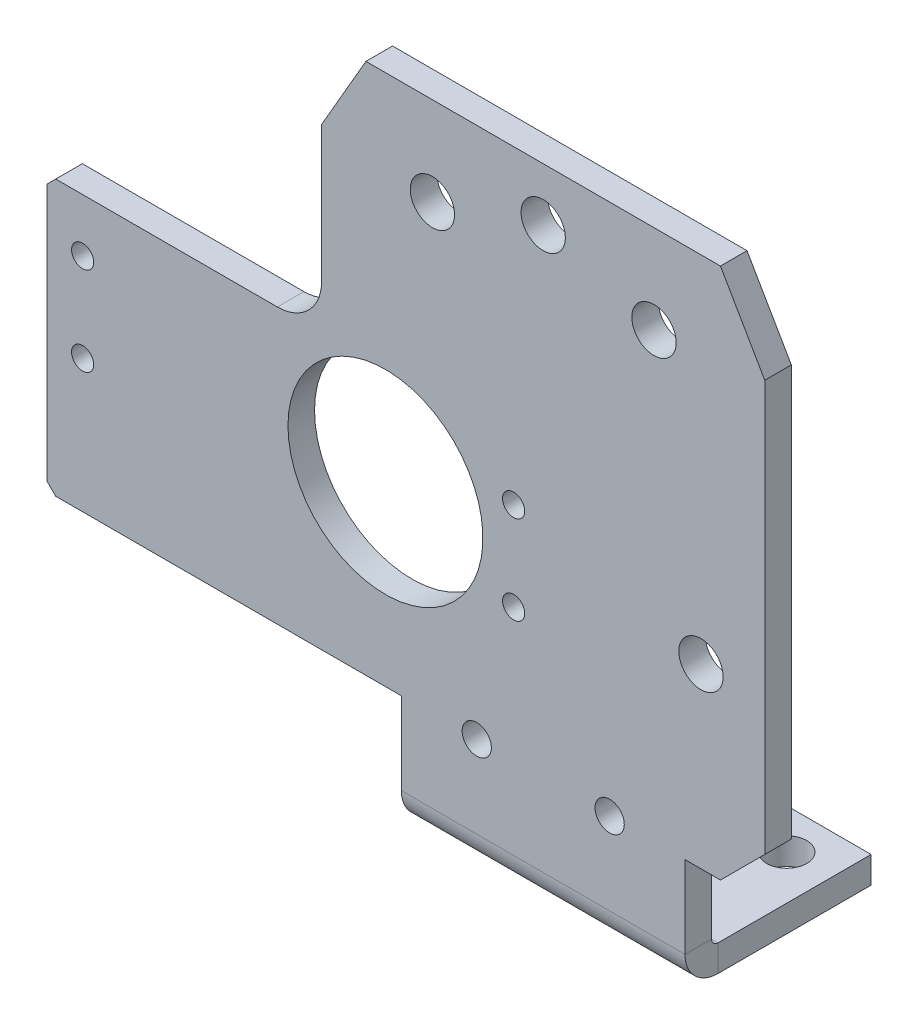
SolidWorks part; units mm, degrees
note: The reader was unsure of these and kept them because the rebuilt part matched: flange length of "边线-法兰1".
material "Q235"
ref_plane "前视基准面" through (0, 0, 0) normal (0, 0, 1) x (1, 0, 0)
ref_plane "上视基准面" through (0, 0, 0) normal (0, 1, 0) x (1, 0, 0)
ref_plane "右视基准面" through (0, 0, 0) normal (1, 0, 0) x (0, 0, -1)
sketch "草图1" plane through (0, 0, 0) normal (0, 0, 1) x (1, 0, 0)
  line L0 (-20, -25) -> (-20, 35) construction
  line L1 (20, -25) -> (16, -25)
  line L2 (16, -25) -> (16, -35)
  line L3 (-16, -25) -> (-56, -25)
  line L4 (-20, -25) -> (-20, -35) construction
  line L5 (-20, 35) -> (20, 35)
  line L6 (20, 35) -> (20, -25) construction
  line L7 (16, -35) -> (-16, -35)
  line L8 (-20, 35) -> (-25, 26.3397)
  line L9 (-56, -25) -> (-56, 6)
  line L10 (-56, 6) -> (-25, 6)
  line L11 (-16, -25) -> (-16, -35)
  line L12 (-20, -35) -> (-16, -35) construction
  line L13 (16, -35) -> (20, -35) construction
  line L14 (20, -25) -> (20, -35) construction
  line L15 (0, -35) -> (0, 35) construction
  line L16 (20, -25) -> (25, -20)
  line L17 (25, 26.3397) -> (20, 35)
  line L18 (25, -20) -> (25, 26.3397)
  line L19 (-25, 26.3397) -> (-25, 6)
  dimension "D1" = 40
  dimension "D2" = 5
  dimension "D3" = 60
  dimension "D4" = 31
  dimension "D5" = 30
  dimension "D6" = 70
  dimension "D7" = 32
  dimension "D8" = 81
  dimension "D9" = 25
  dimension "D10" = 60
  dimension "D11" = 45
  dimension "D12" = 25
base flange "基体-法兰1" sketch "草图1" thickness 3 reverse thickness direction no parameters "D1"=0.7366
sketch "草图6" plane through (0, 0, 0) normal (0, 0, 1) x (1, 0, 0)
  line L0 (0, 0) -> (0, 29) construction
  line L1 (-17.8, -5) -> (17.8, -5) construction
  line L2 (20, 35) -> (-20, 35) construction
  circle A0 centre (-17.8, -5) radius 2.5
  circle A1 centre (17.8, -5) radius 2.5
  circle A2 centre (0, 29) radius 2.5
  circle A3 centre (-12.5, 25) radius 2.5
  circle A4 centre (12.5, 25) radius 2.5
  dimension "D1" = 35.6
  dimension "D3" = 5
  dimension "D5" = 5
  dimension "D6" = 25
  dimension "D7" = 10
  dimension "D8" = 5
  dimension "D2" = 40
  dimension "D4" = 6
extrude "切除-拉伸1" cut sketch "草图6" against normal blind 3 normal cut yes
sketch "草图9" plane through (0, 0, -3) normal (0, 0, -1) x (-1, 0, 0)
  circle A1 centre (17.8, -5) radius 11
  dimension "D1" = 22
extrude "切除-拉伸2" cut sketch "草图9" against normal up to next normal cut yes
hole_wizard "M3 螺纹孔1" positions "草图12" profile "草图13" tap size "M3" standard "Gb"
sketch "草图12" plane through (0, -38, 0) normal (0, 0, 1) x (-1, 0, 0)
  point P0 (51.965, -38)
  point P3 (51.965, -28)
  point P6 (3.335, -28)
  point P9 (3.335, -38)
sketch "草图13" plane through (-51.965, 0, 0) normal (1, 0, 0) x (0, -1, 0)
  line L0 (0, 0) -> (0, 8.2511)
  line L1 (0, 8.2511) -> (1.25, 7.5)
  line L2 (1.25, 7.5) -> (1.25, 0)
  line L3 (1.25, 0) -> (0, 0)
  line L4 (0, 8.2511) -> (-1.25, 7.5) construction
  line L5 (0, -6.35) -> (0, 107.95) construction
  dimension "螺纹孔钻头直径" = 2.5
  dimension "螺纹孔钻头深度" = 7.5
  dimension "导头角度" = 118
cosmetic thread "孔螺蚊线1"
cosmetic thread "孔螺蚊线2"
cosmetic thread "孔螺蚊线3"
cosmetic thread "孔螺蚊线4"
edge flange "边线-法兰1" sketch "草图18" flange angle 90 flange length 18 flange position material outside bend radius 0.7366 thickness 3 relief rectangular parameters "D6"=10
sketch "草图18" plane through (0, -35, -3) normal (0, 1, 0) x (1, 0, 0)
  line L1 (16, 0) -> (-16, 0) construction
  line L2 (-16, 0) -> (-16, 18)
  line L3 (-16, 18) -> (16, 18)
  line L4 (16, 18) -> (16, 0)
  line L5 (16, 0) -> (-16, 0)
bend "边线折弯1" bend radius 0.7366 bend angle 90 parameters "D5"=1
hole_wizard "Ø7.0 (7) 直径孔" positions "草图21" profile "草图22" hole size "Ø7.0" standard "Gb"
sketch "草图21" plane through (-9.85, -35, 1.271) normal (0, 1, 0) x (1, 0, 0)
  point P0 (9.85, 9.75)
sketch "草图22" plane through (0, -35, -8.479) normal (1, 0, 0) x (0, 0, 1)
  line L0 (0, 0) -> (0, 8.103)
  line L1 (0, 8.103) -> (3.5, 6)
  line L2 (3.5, 6) -> (3.5, 0)
  line L3 (3.5, 0) -> (0, 0)
  line L4 (0, 8.103) -> (-3.5, 6) construction
  line L5 (0, -6.35) -> (0, 107.95) construction
  dimension "孔直径" = 7
  dimension "孔深度" = 6
  dimension "导头角度" = 118
fillet "圆角1" radius 5 1 edges at (-25, 6, -1.5)
chamfer "倒角1" distance 1 angle 45 2 edges at (-56, -25, -1.5) (-56, 6, -1.5)
hole_wizard "Ø4.5 (4.5) 直径孔1" positions "草图23" profile "草图24" hole size "Ø4.5" standard "Gb"
sketch "草图23" plane through (-9.85, -35, 1.271) normal (0, 1, 0) x (1, 0, 0)
  point P0 (-1.15, 17.75)
  point P3 (20.85, 17.75)
sketch "草图24" plane through (-11, -35, -16.479) normal (1, 0, 0) x (0, 0, 1)
  line L0 (0, 0) -> (0, 6.3519)
  line L1 (0, 6.3519) -> (2.25, 5)
  line L2 (2.25, 5) -> (2.25, 0)
  line L3 (2.25, 0) -> (0, 0)
  line L4 (0, 6.3519) -> (-2.25, 5) construction
  line L5 (0, -6.35) -> (0, 107.95) construction
  dimension "孔直径" = 4.5
  dimension "孔深度" = 5
  dimension "导头角度" = 118
hole_wizard "M4 螺纹孔1" positions "草图27" profile "草图28" tap size "M4" standard "Gb"
sketch "草图27" plane through (-9.85, -49.5, 0) normal (0, 0, 1) x (-1, 0, 0)
  point P0 (-2.35, -24.5)
  point P3 (-17.35, -24.5)
sketch "草图28" plane through (-7.5, -25, 0) normal (1, 0, 0) x (0, -1, 0)
  line L0 (0, 0) -> (0, 12.4914)
  line L1 (0, 12.4914) -> (1.65, 11.5)
  line L2 (1.65, 11.5) -> (1.65, 0)
  line L3 (1.65, 0) -> (0, 0)
  line L4 (0, 12.4914) -> (-1.65, 11.5) construction
  line L5 (0, -6.35) -> (0, 107.95) construction
  dimension "螺纹孔钻头直径" = 3.3
  dimension "螺纹孔钻头深度" = 11.5
  dimension "导头角度" = 118
cosmetic thread "孔螺蚊线5"
cosmetic thread "孔螺蚊线6"
sketch "折弯-线1" plane through (0, 0, 0) normal (0, 1, 0) x (1, 0, 0)
sketch "边界框1" plane through (0, 0, 0) normal (0, 1, 0) x (1, 0, 0)
sheet metal parameters "钣金(11)" thickness 3 parameters "D1"=0.7366
flat pattern "平板型式(11)" [suppressed]
sketch "折弯-线2" plane through (0, 0, 0) normal (0, 1, 0) x (1, 0, 0)
sketch "边界框2" [suppressed] plane through (0, 0, 0) normal (0, 1, 0) x (1, 0, 0)
sheet metal parameters "钣金(12)" thickness 3 parameters "D1"=0.7366
flat pattern "平板型式(11)"
sketch "折弯-线3" plane through (0, 0, 0) normal (0, 1, 0) x (1, 0, 0)
sketch "边界框3" [suppressed] plane through (0, 0, 0) normal (0, 1, 0) x (1, 0, 0)
sheet metal parameters "钣金(13)" thickness 3 parameters "D1"=0.7366
flat pattern "平板型式(11)"
sketch "折弯-线4" plane through (0, 0, 0) normal (0, 1, 0) x (1, 0, 0)
sketch "边界框4" [suppressed] plane through (0, 0, 0) normal (0, 1, 0) x (1, 0, 0)
sheet metal parameters "钣金(14)" thickness 3 parameters "D1"=0.7366
flat pattern "平板型式(11)"
sketch "折弯-线5" plane through (0, 0, 0) normal (0, 1, 0) x (1, 0, 0)
sketch "边界框5" [suppressed] plane through (0, 0, 0) normal (0, 1, 0) x (1, 0, 0)
sheet metal parameters "钣金(15)" thickness 3 parameters "D1"=0.7366
flat pattern "平板型式(11)" [suppressed]
sketch "折弯-线6" plane through (0, 0, 0) normal (0, 1, 0) x (1, 0, 0)
sketch "边界框6" [suppressed] plane through (0, 0, 0) normal (0, 1, 0) x (1, 0, 0)
bend of the flat pattern "展开-<边线折弯1>1"
sheet metal parameters "钣金(16)" thickness 3 parameters "D1"=0.7366
flat pattern "平板型式(11)" [suppressed]
sketch "折弯-线7" plane through (0, 0, 0) normal (0, 1, 0) x (1, 0, 0)
sketch "边界框7" [suppressed] plane through (0, 0, 0) normal (0, 1, 0) x (1, 0, 0)
bend of the flat pattern "展开-<边线折弯1>2"
sheet metal parameters "钣金(17)" thickness 3 parameters "D1"=0.7366
flat pattern "平板型式(11)" [suppressed]
sketch "折弯-线8" plane through (0, 0, 0) normal (0, 1, 0) x (1, 0, 0)
sketch "边界框8" [suppressed] plane through (0, 0, 0) normal (0, 1, 0) x (1, 0, 0)
bend of the flat pattern "展开-<边线折弯1>3"
sheet metal parameters "钣金(18)" thickness 3 parameters "D1"=0.7366
flat pattern "平板型式(11)" [suppressed]
sketch "折弯-线9" plane through (0, 0, 0) normal (0, 1, 0) x (1, 0, 0)
sketch "边界框9" [suppressed] plane through (0, 0, 0) normal (0, 1, 0) x (1, 0, 0)
bend of the flat pattern "展开-<边线折弯1>4"
